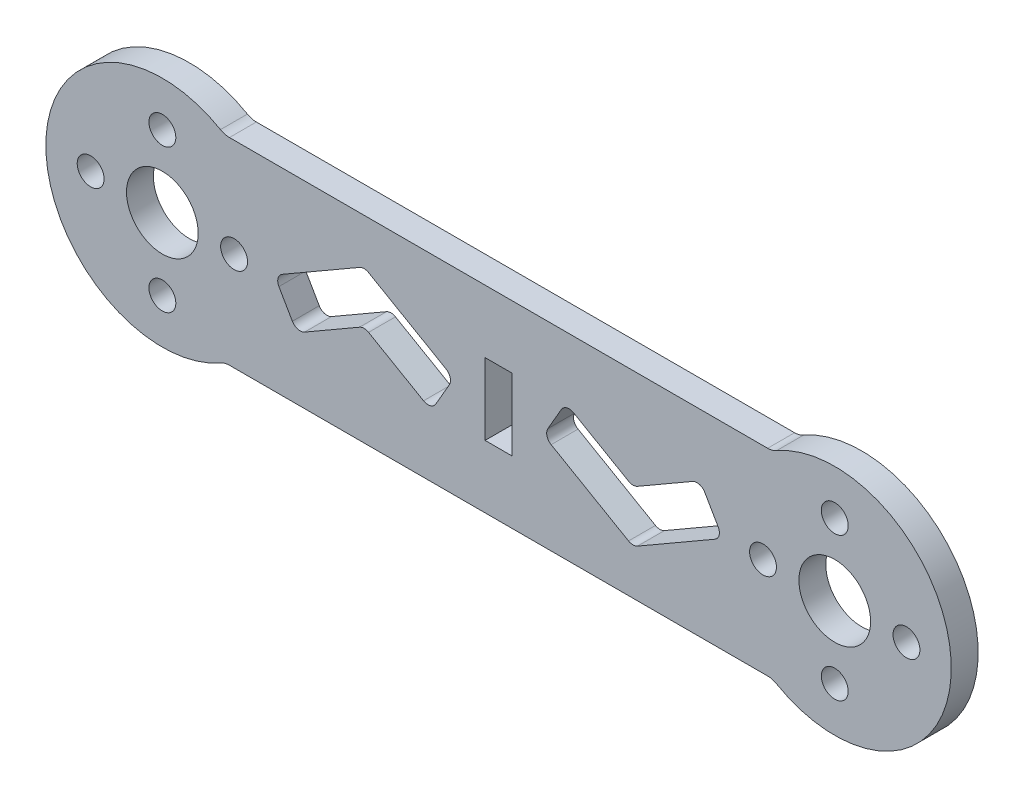
SolidWorks part; units mm, degrees
material "Stop 1060"
ref_plane "Przednia" through (0, 0, 0) normal (0, 0, 1) x (1, 0, 0)
ref_plane "Górna" through (0, 0, 0) normal (0, 1, 0) x (1, 0, 0)
ref_plane "Prawa" through (0, 0, 0) normal (1, 0, 0) x (0, 0, -1)
sketch "Szkic1" plane through (0, 0, 0) normal (0, 0, 1) x (1, 0, 0)
  line L0 (0, 11) -> (0, -11) construction
  line L1 (-30.5718, -11) -> (30.5718, -11)
  line L2 (-50.5, 0) -> (50.5, 0) construction
  line L3 (-30.5718, 11) -> (30.5718, 11)
  line L4 (0, 0) -> (-30.5718, -11) construction
  line L5 (0, 0) -> (30.5718, 11) construction
  line L6 (0, 0) -> (30.5718, -11) construction
  line L7 (0, 0) -> (-30.5718, 11) construction
  arc A0 (30.5718, -11) -> (30.5718, 11) centre (37.5, 0) ccw
  arc A1 (-30.5718, -11) -> (-30.5718, 11) centre (-37.5, 0) cw
  circle A2 centre (37.5, 0) radius 4
  circle A3 centre (-37.5, 0) radius 4
  point P0 (0, 0)
  dimension "D1" = 75
  dimension "D2" = 13
  dimension "D3" = 8
  dimension "D4" = 22
extrude "Dodanie-wyciągnięcie1" add sketch "Szkic1" along normal blind 3
sketch "Szkic2" plane through (0, 0, 3) normal (0, 0, 1) x (1, 0, 0)
  line L0 (37.5, 13) -> (37.5, -13) construction
  line L1 (37.5, 0) -> (50.5, 0) construction
  arc A0 (30.5718, -11) -> (30.5718, 11) centre (37.5, 0) ccw construction
  circle A1 centre (45.5, 0) radius 1.5
  circle A2 centre (37.5, -8) radius 1.5
  circle A3 centre (29.5, 0) radius 1.5
  circle A4 centre (37.5, 8) radius 1.5
  point P21 (37.5, 0)
  dimension "D1" = 8
  dimension "D4" = 3
  dimension "D2" = 8
  dimension "D3" = 4
extrude "Wytnij-wyciągnięcie1" cut sketch "Szkic2" against normal through all contours A3 | A4 | A2 | A1
mirror "Lustro1" about plane through (0, 0, 0) normal (1, 0, 0) of "Wytnij-wyciągnięcie1"
fillet "Zaokrąglenie1" radius 2 4 edges at (-30.5718, -11, 1.5) (-30.5718, 11, 1.5) (30.5718, 11, 1.5) (30.5718, -11, 1.5)
sketch "Szkic6" plane through (0, 0, 3) normal (0, 0, 1) x (1, 0, 0)
  line L0 (-37.5, 0) -> (37.5, 0) construction
  line L1 (0, 11) -> (0, -11) construction
  line L2 (30.0167, 11) -> (-30.0167, 11) construction
  line L3 (-30.0167, -11) -> (30.0167, -11) construction
  line L4 (-15, 6) -> (-25, 0.2265)
  line L5 (-15, 6) -> (-5, 0.2265)
  line L6 (-25, 0.2265) -> (-22.5, -4.1036)
  line L9 (-22.5, -4.1036) -> (-15, 0.2265)
  line L10 (-15, 0.2265) -> (-7.5, -4.1036)
  line L11 (-7.5, -4.1036) -> (-5, 0.2265)
  line L12 (25, -0.2265) -> (22.5, 4.1036)
  line L13 (22.5, 4.1036) -> (15, -0.2265)
  line L14 (15, -0.2265) -> (7.5, 4.1036)
  line L15 (7.5, 4.1036) -> (5, -0.2265)
  line L16 (15, -6) -> (5, -0.2265)
  line L17 (15, -6) -> (25, -0.2265)
  point P22 (-1, 0)
  point P23 (0, 0)
  dimension "D1" = 30
  dimension "D2" = 30
  dimension "D3" = 10
  dimension "D4" = 10
  dimension "D5" = 15
  dimension "D6" = 5
  dimension "D7" = 5
  dimension "D8" = 6
  dimension "D9" = 2
extrude "Wytnij-wyciągnięcie6" cut sketch "Szkic6" against normal blind 10
fillet "Zaokrąglenie2" radius 1 12 edges at (7.5, 4.1036, 1.5) (5, -0.2265, 1.5) (15, -6, 1.5) (25, -0.2265, 1.5) (22.5, 4.1036, 1.5) (15, -0.2265, 1.5) (-15, 6, 1.5) (-5, 0.2265, 1.5) (-7.5, -4.1036, 1.5) (-15, 0.2265, 1.5) (-22.5, -4.1036, 1.5) (-25, 0.2265, 1.5)
sketch "Szkic7" plane through (0, 0, 3) normal (0, 0, 1) x (1, 0, 0)
  line L1 (-1.5, 4) -> (1.5, 4)
  line L2 (-1.5, 4) -> (-1.5, -4)
  line L3 (-1.5, -4) -> (1.5, -4)
  line L4 (1.5, 4) -> (1.5, -4)
  line L5 (-1.5, 4) -> (1.5, -4) construction
  line L6 (-1.5, -4) -> (1.5, 4) construction
  point P0 (0, 0)
  dimension "D1" = 3
  dimension "D2" = 8
extrude "Wytnij-wyciągnięcie7" cut sketch "Szkic7" against normal blind 10
